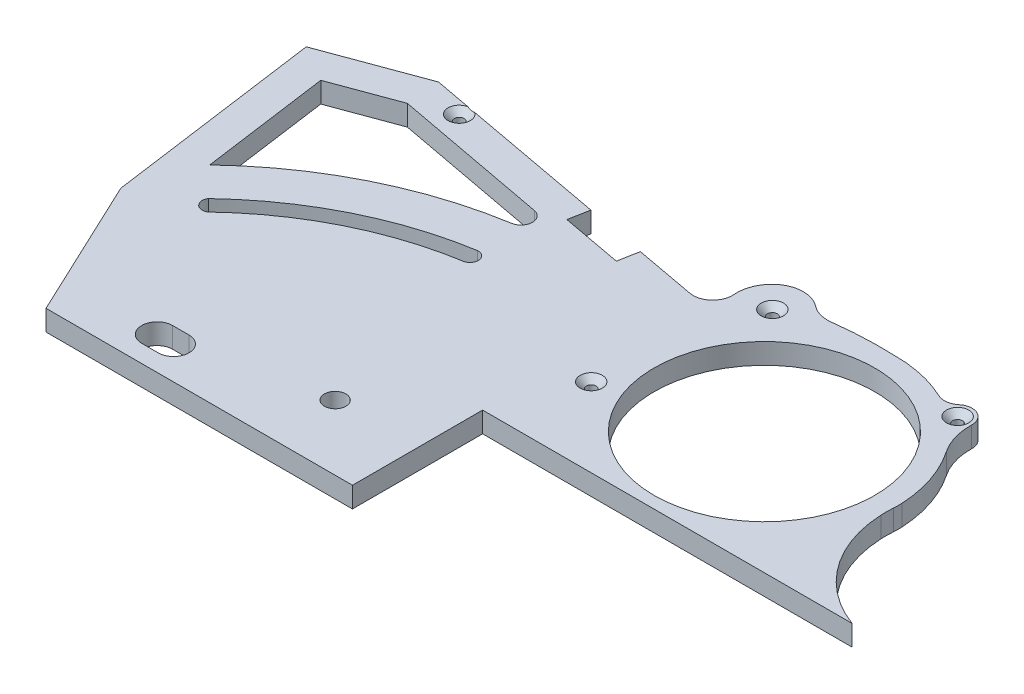
SolidWorks part; units mm, degrees
ref_plane "Front Plane" through (0, 0, 0) normal (0, 0, 1) x (1, 0, 0)
ref_plane "Top Plane" through (0, 0, 0) normal (0, 1, 0) x (1, 0, 0)
ref_plane "Right Plane" through (0, 0, 0) normal (1, 0, 0) x (0, 0, -1)
sketch "Sketch1" plane through (0, 0, 0) normal (0, 1, 0) x (1, 0, 0)
  line L0 (-48.4644, 25.4738) -> (-67.195, 28.948)
  line L1 (-142.1171, 42.8447) -> (-142.9856, 38.1621) construction
  line L2 (-164.2302, -34.2094) -> (-143.6929, -77.8139)
  line L3 (-49.2049, -37.6819) -> (-49.2049, -77.8139)
  line L4 (-49.2049, -77.8139) -> (-76.5633, -77.8139)
  line L5 (-142.7166, 32.6227) -> (-162.215, 25.4248)
  line L6 (-162.215, 25.4248) -> (-156.7262, -14.2919)
  line L7 (-162.215, 25.4248) -> (-154.1658, -32.8186) construction
  line L8 (-114.5088, -67.653) -> (-119.5888, -67.653) construction
  line L9 (-117.0488, -49.2806) -> (-117.0488, -125.4806) construction
  line L10 (-143.6125, 43.1221) -> (-173.3978, 32.1269)
  line L11 (-173.3978, 32.1269) -> (-164.2302, -34.2094)
  line L12 (-94.5262, 23.5926) -> (-142.7166, 32.6227)
  line L13 (-50.3173, 15.4842) -> (-142.7166, 32.6227) construction
  line L14 (-143.6515, 36.6711) -> (-124.5446, 33.1271) construction
  line L15 (-143.6515, 36.6711) -> (-145.7426, 42.3358) construction
  line L16 (-49.6225, 19.2303) -> (-48.4644, 25.4738) construction
  line L17 (-143.6515, 36.6711) -> (-172.5514, 26.0027) construction
  line L18 (-104.656, 35.8964) -> (-123.3865, 39.3706)
  line L19 (-119.6498, 33.5204) -> (-173.6416, 43.6376) construction
  line L20 (-130.2339, 30.2836) -> (-128.3767, 40.2961) construction
  line L21 (-123.3865, 39.3706) -> (-143.6125, 43.1221)
  line L22 (-48.4644, 25.4738) -> (-143.6125, 43.1221) construction
  line L23 (-85.9255, 32.4222) -> (-87.0836, 26.1787)
  line L24 (-68.353, 22.7045) -> (-67.195, 28.948)
  line L25 (-85.9255, 32.4222) -> (-104.656, 35.8964)
  line L26 (-87.0836, 26.1787) -> (-68.353, 22.7045)
  line L27 (-49.2049, -37.6819) -> (45.278, -37.6819)
  line L28 (-143.6929, -77.8139) -> (-76.5633, -77.8139)
  line L29 (-114.5088, -72.4155) -> (-119.5888, -72.4155)
  line L30 (-114.5088, -62.8905) -> (-119.5888, -62.8905)
  line L31 (-49.2049, -37.6819) -> (45.278, -37.6819) construction
  line L32 (-49.2049, -37.6819) -> (45.278, -37.6819) construction
  line L33 (-49.2049, -37.6819) -> (45.278, -37.6819) construction
  line L34 (45.278, -37.6819) -> (64.7267, -37.6819)
  line L35 (-105.8141, 29.6529) -> (-49.6225, 19.2303) construction
  circle A0 centre (0, 0) radius 34.036
  arc A1 (40.304, -0.5649) -> (40.3286, 2.1532) centre (18.5528, 0.9906) ccw
  arc A2 (40.3286, 2.1532) -> (33.4191, 22.6758) centre (0, 0) ccw
  arc A3 (40.304, -0.5649) -> (40.2565, -4.3649) centre (72.5057, -2.8677) ccw
  arc A4 (0, 40.386) -> (-18.9447, 39.5692) centre (-4.6204, -72.5606) ccw
  arc A5 (-38.2002, 40.515) -> (-41.3257, 31.9049) centre (-30.3114, 32.779) ccw
  arc A6 (-48.4644, 25.4738) -> (-41.3257, 31.9049) centre (-47.3604, 31.4259) ccw
  circle A7 centre (-31.3995, 33.846) radius 1.524
  circle A8 centre (-31.3995, 33.846) radius 6.35 construction
  arc A9 (-25.5638, 41.374) -> (-38.2002, 40.515) centre (-31.3995, 33.846) ccw
  circle A10 centre (-117.0488, -67.653) radius 76.2 construction
  arc A11 (-25.5638, 41.374) -> (-18.9447, 39.5692) centre (-20.0791, 48.4493) ccw
  arc A12 (-114.5088, -72.4155) -> (-114.5088, -62.8905) centre (-114.5088, -67.653) ccw
  circle A13 centre (-74.6049, -57.7479) radius 3.302
  arc A14 (-94.6028, 16.657) -> (-94.5262, 23.5926) centre (-95.1682, 20.1315) ccw
  arc A15 (-156.7262, -14.2919) -> (-94.6028, 16.657) centre (-75.7968, -98.9161) cw
  arc A16 (-119.5888, -62.8905) -> (-119.5888, -72.4155) centre (-119.5888, -67.653) ccw
  circle A17 centre (-40.0207, -13.3674) radius 1.524
  arc A18 (64.7267, -37.6819) -> (40.2565, -4.3649) centre (77.5287, -2.6345) cw
  circle A19 centre (-131.8085, 37.7035) radius 1.524
  circle A20 centre (-131.8085, 37.7035) radius 1.524 construction
  circle A21 centre (-40.0207, -13.3674) radius 2.0417 construction
  arc A22 (-147.9485, -23.4703) -> (-92.5631, 4.1219) centre (-75.7968, -98.9161) cw
  arc A23 (-144.4375, -27.1417) -> (-91.7472, -0.8921) centre (-75.7968, -98.9161) cw
  arc A24 (-147.9485, -23.4703) -> (-144.4375, -27.1417) centre (-145.815, -24.9444) ccw
  arc A25 (-91.7472, -0.8921) -> (-92.5631, 4.1219) centre (-92.3612, 1.5814) ccw
  circle A26 centre (25.7279, 33.846) radius 1.524
  arc A27 (30.1715, 33.7352) -> (22.862, 37.2438) centre (25.7279, 33.846) ccw
  arc A28 (17.2569, 36.5134) -> (22.862, 37.2438) centre (19.4911, 41.2406) ccw
  arc A29 (30.1715, 33.7352) -> (33.4191, 22.6758) centre (49.0256, 33.2653) ccw
  arc A30 (17.2569, 36.5134) -> (0, 40.386) centre (0, 0) ccw
  point P60 (-117.0488, -67.653)
  dimension "D1" = 68.072
  dimension "D2" = 12.7
  dimension "D3" = 19.05
  dimension "D6" = 3.048
  dimension "D4" = 152.4
  dimension "D9" = 6.35
  dimension "D10" = 6.604
  dimension "D18" = 3.048
  dimension "D14" = 3.048
  dimension "D20" = 3.048
  dimension "D21" = 8.89
  dimension "D5" = 40.132
  dimension "D7" = 127
  dimension "D8" = 76.2
  dimension "D11" = 31.75
  dimension "D13" = 95.25
  dimension "D15" = 5.1308
  dimension "D16" = 10.25
  dimension "D17" = 19.05
  dimension "D19" = 12.7
  dimension "D12" = 10.16
extrude "Boss-Extrude1" add sketch "Sketch1" along normal blind 6.35
chamfer "Chamfer1" distance 1.905 angle 45 4 edges at (-40.0207, 6.35, 14.8914) (-31.3995, 6.35, -32.322) (-131.8085, 6.35, -36.1795) (25.7279, 6.35, -32.322)
sketch "Sketch2" plane through (1.7978, 0, -9.6927) normal (0.1824, 0, -0.9832) x (-0.9832, 0, -0.1824)
  line L0 (71.3474, 3.175) -> (90.3974, 3.175) construction
  line L1 (71.3474, 6.35) -> (71.3474, 0) construction
  line L2 (90.3974, 6.35) -> (90.3974, 0) construction
  line L3 (80.8724, 0) -> (80.8724, 6.35) construction
  line L4 (71.3474, 0) -> (90.3974, 0) construction
  line L5 (71.3474, 6.35) -> (90.3974, 6.35) construction
  circle A0 centre (80.8724, 3.175) radius 1.1303
  dimension "D1" = 2.2606
extrude "Cut-Extrude1" cut sketch "Sketch2" against normal blind 12.7
